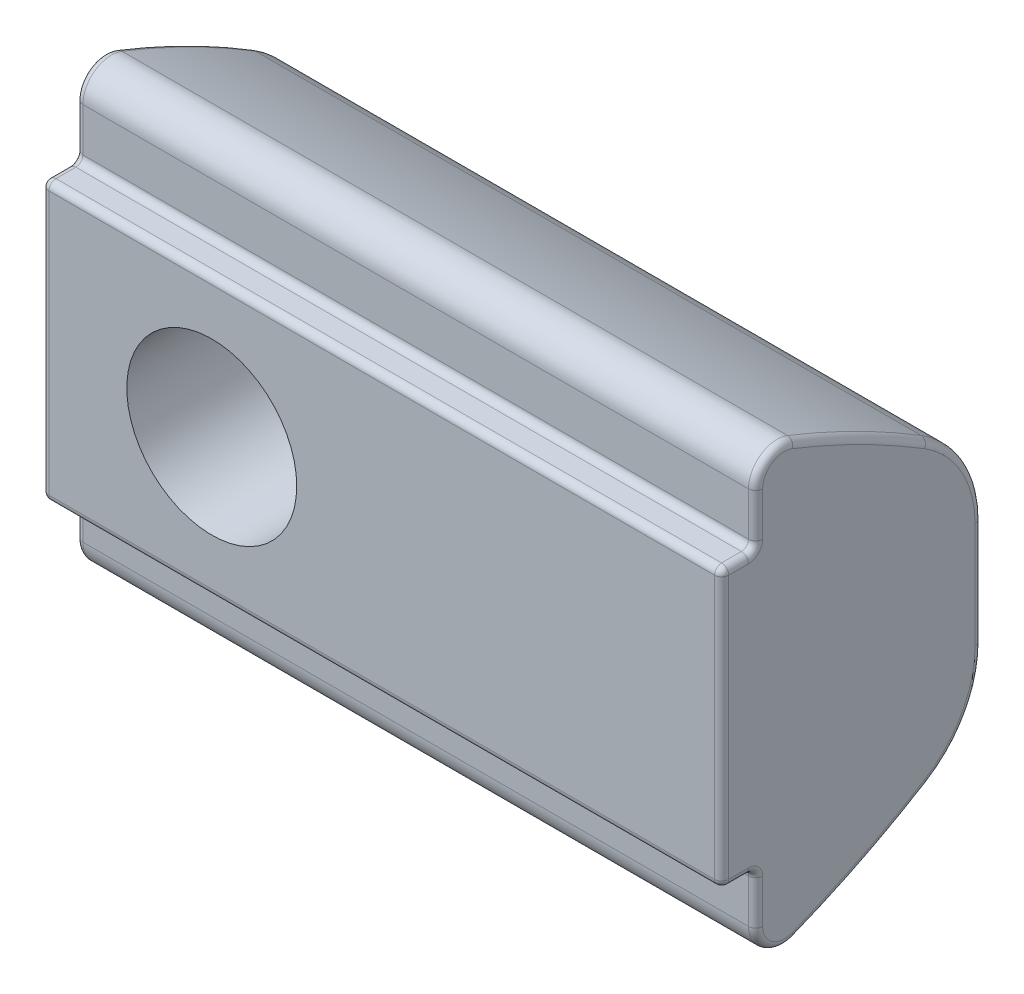
SolidWorks part; units mm, degrees
material "Galvanized Steel"
ref_plane "Front Plane" through (0, 0, 0) normal (0, 0, 1) x (1, 0, 0)
ref_plane "Top Plane" through (0, 0, 0) normal (0, 1, 0) x (1, 0, 0)
ref_plane "Right Plane" through (0, 0, 0) normal (1, 0, 0) x (0, 0, -1)
sketch "Sketch1" plane through (0, 0, 0) normal (0, 0, 1) x (1, 0, 0)
  line L0 (0, 3.85) -> (0, -3.85) construction
  line L1 (-6, 3.85) -> (6, 3.85) construction
  line L2 (-6, 3.85) -> (-6, -3.85) construction
  line L3 (-6, -3.85) -> (6, -3.85) construction
  line L4 (6, 3.85) -> (6, -3.85) construction
  line L5 (-6, 0) -> (6, 0) construction
  circle A1 centre (-3, 0) radius 1.5 construction
  point P5 (0, 0)
  point P12 (-3, -1.5)
  point P14 (-3, 1.5)
  dimension "D3" = 3
  dimension "Thread Diameter" = 3
  dimension "Length" = 12
  dimension "Width" = 7.7
sketch "Sketch2" plane through (0, 0, 0) normal (1, 0, 0) x (0, 0, -1)
  line L0 (-2.3, 0) -> (2.3, 0) construction
  line L1 (-2.7688, 1.5541) -> (-2.5188, 1.1211)
  line L2 (-2.3, 2.45) -> (-2.3, -2.45) construction
  line L3 (-2.5188, 1.1211) -> (-2.2688, 1.5541)
  line L4 (-2.2688, 1.5541) -> (-2.7688, 1.5541)
  line L5 (-2.5188, 1.5541) -> (-2.5188, 1.5)
  line L6 (-2.5188, 1.1211) -> (-2.5188, 1.1752)
  line L7 (-2.7375, 1.5) -> (-2.3, 1.5)
  line L8 (-2.7531, 1.5271) -> (-2.2844, 1.5271)
  line L9 (-2.55, 1.1752) -> (-2.4875, 1.1752)
  point P3 (0, 0)
  point P6 (-2.3, 0)
  point P7 (-1.7, 0)
  point P8 (3.3, 0)
  point P9 (-2.3, -1.5)
  point P11 (-2.3, 1.5)
  point P22 (-2.5188, 1.5)
  point P25 (-2.5188, 1.5271)
  point P28 (-2.5188, 1.1752)
  dimension "D1" = 4.9
  dimension "D2" = 0.6
  dimension "Thickness" = 4.6
  dimension "Ball Offset" = 1
  dimension "Thread Pitch" = 0.5
  dimension "D6" = 0.0625
sketch "Sketch3" plane through (0, 0, 0) normal (1, 0, 0) x (0, 0, -1)
  line L0 (-2.3, 2.45) -> (-1.7, 2.45)
  line L1 (-1.7, 2.45) -> (-1.7, 3.345)
  line L2 (-2.3, 2.45) -> (-2.3, -2.45)
  line L3 (-2.3, -2.45) -> (-1.7, -2.45)
  line L4 (-1.7, -2.45) -> (-1.7, -3.345)
  line L7 (2.3, 0.9333) -> (2.3, -0.9333)
  arc A0 (-1.0099, 3.8148) -> (1.3476, 2.637) centre (-6.5094, -10.1406) cw
  arc A1 (-1.0099, -3.8148) -> (1.3476, -2.637) centre (-6.5094, 10.1406) ccw
  arc A4 (-1.0099, -3.8148) -> (-1.7, -3.345) centre (-1.195, -3.345) cw
  arc A5 (-1.7, 3.345) -> (-1.0099, 3.8148) centre (-1.195, 3.345) cw
  arc A6 (1.3476, -2.637) -> (2.3, -0.9333) centre (0.3, -0.9333) ccw
  arc A7 (2.3, 0.9333) -> (1.3476, 2.637) centre (0.3, 0.9333) ccw
  point P20 (2.3, -2)
  point P23 (2.3, 2)
  point P32 (-1.195, 3.85)
  dimension "D1" = 0.505
  dimension "D2" = 15
  dimension "D4" = 2
  dimension "D3" = 4
extrude "Boss-Extrude1" add sketch "Sketch3" against normal up to vertex (6 mm away) and the other way up to vertex (6 mm away) up to point (-6, 0, 0) other way up to point (6, 3.85, 0)
sketch "Sketch4" plane through (0, 0, -2.3) normal (0, 0, -1) x (-1, 0, 0)
  line L0 (6, 0) -> (-6, 0) construction
  circle A0 centre (-3, 0) radius 1.5
  dimension "D1" = 3
  dimension "D2" = 6
extrude "Cut-Extrude1" cut sketch "Sketch4" against normal blind 3
ref_plane "Plane1" through (3, 0, 0) normal (1, 0, 0) x (0, 0, -1)
sketch "Sketch5" plane through (3, 0, 0) normal (1, 0, 0) x (0, 0, -1)
  line L0 (2.3, -1.5) -> (2.3, 1.5) construction
  line L1 (2.3, -1.5) -> (2.3, 1.5) construction
  line L2 (-2.3, 0) -> (2.3, 0) construction
  line L3 (0.3, 0) -> (3.3, 0)
  arc A0 (3.3, 0) -> (0.3, 0) centre (1.8, 0) ccw
  point P9 (1.8, 1.5)
revolve "Revolve1" add sketch "Sketch5" angle 360 about L3
sketch "Sketch6" plane through (0, 0, 2.3) normal (0, 0, 1) x (1, 0, 0)
  circle A0 centre (-3, 0) radius 1.5 construction
  circle A1 centre (-3, 0) radius 1.5
extrude "Cut-Extrude2" cut sketch "Sketch6" against normal through all
fillet "Fillet4" radius 0.1 4 edges at (2.8466, -1.4921, -2.2203) (4.5, 0, -2.3) (3.1534, 1.4921, -2.2203) (1.5, 0, -2.3)
fillet "Fillet3" radius 0.125 28 edges at (-6, 0, -2.3) (-6, -3.2778, -0.1948) (-6, 3.2778, -0.1948) (-6, -3.7624, 1.4792) (-6, 3.7624, 1.4792) (-6, -2.8975, 1.7) (-6, 2.8975, 1.7) (6, -2.8975, 1.7) (6, -3.7624, 1.4792) (6, -3.2778, -0.1948) (6, 0, -2.3) (6, 2.8975, 1.7) (6, 3.7624, 1.4792) (-6, -2.45, 2) (0, -2.45, 2.3) (6, -2.45, 2) (0, -2.45, 1.7) (-6, 2.45, 2) (0, 2.45, 1.7) (6, 2.45, 2) (0, 2.45, 2.3) (-6, 0, 2.3) (6, 0, 2.3) (6, 3.2778, -0.1948) (-6, -1.9092, -2.0457) (-6, 1.9092, -2.0457) (6, -1.9092, -2.0457) (6, 1.9092, -2.0457)
sketch "Sketch8" plane through (0, 0, 0) normal (0, 0, 1) x (1, 0, 0)
  line L0 (-3, 0) -> (-1.9393, -1.0607)
  line L1 (-6, 0) -> (6, 0) construction
  circle A0 centre (-3, 0) radius 1.5 construction
  circle A1 centre (-3, 0) radius 1.5
  point P0 (-6, 3.85)
  point P1 (6, 3.85)
  point P3 (-6, -3.85)
  point P13 (-1.9393, -1.0607)
  dimension "D1" = 45
sketch "Sketch9" plane through (0, 0, 0) normal (1, 0, 0) x (0, 0, -1)
  line L0 (2.3, -1.5) -> (2.3, 1.5) construction
  line L1 (2.3, -1.5) -> (2.3, 1.5)
  point P0 (-2.3, 2.45)
  point P1 (2.3, 1.5)
  point P2 (-2.3, -2.45)
  point P7 (3.3, 0)
ref_plane "Plane2" [suppressed] through (-3, 0, 0) normal (1, 0, 0) x (0, 0, -1)
sketch "Sketch10" [suppressed] plane through (0, 0, 2.3) normal (0, 0, 1) x (1, 0, 0)
  circle A0 centre (-3, 0) radius 1.5 construction
  circle A1 centre (-3, 0) radius 1.5
curve "Helix/Spiral1" [suppressed] pitch 0.5 height 5.1 turns 10.2
sketch "Sketch11" [suppressed] plane through (-3, 0, 0) normal (1, 0, 0) x (0, 0, -1)
  line L0 (-2.55, 1.1752) -> (-2.4875, 1.1752) construction
  line L1 (-2.5188, 1.1211) -> (-2.2688, 1.5541) construction
  line L2 (-2.7688, 1.5541) -> (-2.5188, 1.1211) construction
  line L3 (-2.7531, 1.5271) -> (-2.2844, 1.5271) construction
  line L4 (-2.55, 1.1752) -> (-2.4875, 1.1752)
  line L5 (-2.4875, 1.1752) -> (-2.2844, 1.5271)
  line L6 (-2.7531, 1.5271) -> (-2.55, 1.1752)
  line L7 (-2.7531, 1.5271) -> (-2.2844, 1.5271)
sweep "Sweep1" [suppressed] add profiles "Sketch11" path "Helix/Spiral1"
sketch "Sketch12" [suppressed] plane through (0, 0, 2.3) normal (0, 0, 1) x (1, 0, 0)
  circle A0 centre (-3, 0) radius 1.5541
  point P4 (-3, 1.5541)
extrude "Cut-Extrude4" [suppressed] cut sketch "Sketch12" along normal through all and the other way through all draft 45
sketch "Sketch14" [suppressed] plane through (6, 0, 0) normal (1, 0, 0) x (0, 0, -1)
  line L0 (2.3, 0.9333) -> (2.3, -0.9333) construction
  line L1 (2.3, 0.9333) -> (2.3, -0.9333)
  line L2 (1.3476, 2.637) -> (6.6216, 2.637)
  line L3 (6.6216, 2.637) -> (6.6216, -2.637)
  line L4 (6.6216, -2.637) -> (1.3476, -2.637)
  arc A0 (1.3476, -2.637) -> (2.3, -0.9333) centre (0.3, -0.9333) ccw construction
  arc A1 (2.3, 0.9333) -> (1.3476, 2.637) centre (0.3, 0.9333) ccw construction
  arc A2 (1.3476, -2.637) -> (2.3, -0.9333) centre (0.3, -0.9333) ccw
  arc A3 (2.3, 0.9333) -> (1.3476, 2.637) centre (0.3, 0.9333) ccw
extrude "Cut-Extrude6" [suppressed] cut sketch "Sketch14" against normal through all
sketch "Sketch13" [suppressed] plane through (0, 0, -2.3) normal (0, 0, -1) x (-1, 0, 0)
  circle A0 centre (3, 0) radius 1.5541 construction
  circle A3 centre (3, 0) radius 1.5795
  dimension "D1" = 0.0254
extrude "Cut-Extrude5" [suppressed] cut sketch "Sketch13" along normal through all and the other way through all draft 45
equation "\"D6@Sketch2\" = \"Thread Pitch@Sketch2\" / 8"
equation "\"D3@Helix/Spiral1\" = \"Thickness@Sketch2\" + \"Thread Pitch@Sketch2\""
equation "\"D4@Helix/Spiral1\" = \"Thread Pitch@Sketch2\""
